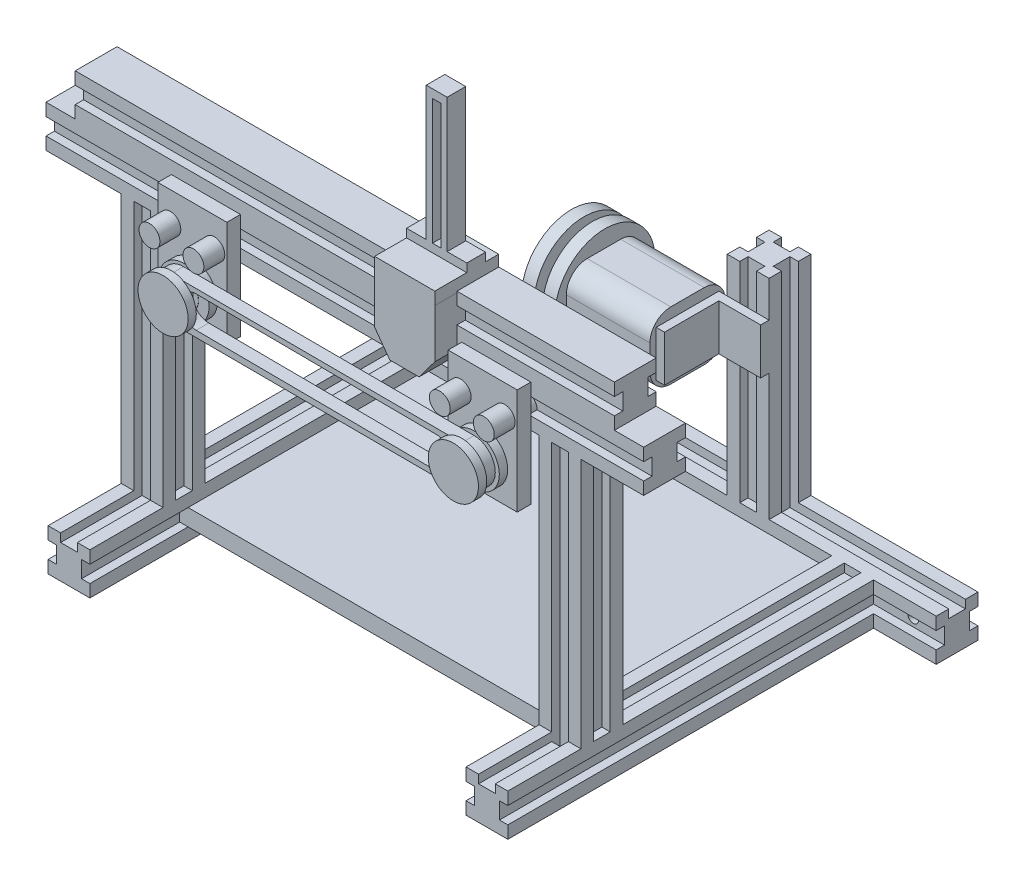
SolidWorks part; units mm, degrees
ref_plane "前基準面" through (0, 0, 0) normal (0, 0, 1) x (1, 0, 0)
ref_plane "上基準面" through (0, 0, 0) normal (0, 1, 0) x (1, 0, 0)
ref_plane "右基準面" through (0, 0, 0) normal (1, 0, 0) x (0, 0, -1)
sketch "草圖1" plane through (0, 0, 0) normal (0, 1, 0) x (1, 0, 0)
  line L1 (-5, 17.5) -> (5, 17.5)
  line L2 (-5, 17.5) -> (-5, -17.5)
  line L3 (-5, -17.5) -> (5, -17.5)
  line L4 (5, 17.5) -> (5, -17.5)
  line L5 (-5, 17.5) -> (5, -17.5) construction
  line L6 (-5, -17.5) -> (5, 17.5) construction
  point P0 (0, 0)
  dimension "D1" = 10
  dimension "D2" = 35
extrude "填料-伸長1" add sketch "草圖1" along normal blind 10
sketch "草圖2" plane through (0, 10, 0) normal (0, 1, 0) x (1, 0, 0)
  line L1 (-5, 17.5) -> (5, 17.5)
  line L2 (-5, 17.5) -> (-5, 27.5)
  line L3 (-5, 27.5) -> (5, 27.5)
  line L4 (5, 17.5) -> (5, 27.5)
  dimension "D1" = 10
extrude "填料-伸長2" add sketch "草圖2" along normal blind 60 and the other way blind 10
sketch "草圖3" plane through (0, 10, 0) normal (0, 1, 0) x (1, 0, 0)
  line L0 (0, -1017.5) -> (0, 48982.5) construction
  line L1 (-5, -17.5) -> (5, -17.5) construction
  line L2 (-5, 17.5) -> (5, 17.5) construction
  line L3 (-2, 17.5) -> (2, 17.5)
  line L4 (-2, 17.5) -> (-2, -17.5)
  line L5 (-2, -17.5) -> (2, -17.5)
  line L6 (2, 17.5) -> (2, -17.5)
  point P5 (0, -17.5)
  dimension "D1" = 2
  dimension "D2" = 2
extrude "除料-伸長1" cut sketch "草圖3" against normal blind 2
sketch "草圖5" plane through (0, 0, -17.5) normal (0, 0, 1) x (1, 0, 0)
  line L0 (0, -940) -> (0, 49060) construction
  line L1 (-5, 70) -> (5, 70) construction
  line L3 (-2, 8) -> (2, 8)
  line L4 (-2, 8) -> (-2, 70)
  line L5 (-2, 70) -> (2, 70)
  line L6 (2, 8) -> (2, 70)
  point P5 (0, 70)
  dimension "D1" = 0
extrude "除料-伸長2" cut sketch "草圖5" against normal blind 2
sketch "草圖6" plane through (0, 70, 0) normal (0, 1, 0) x (1, 0, 0)
  line L1 (-5, 27.5) -> (5, 27.5)
  line L2 (-5, 27.5) -> (-5, 17.5)
  line L3 (-5, 17.5) -> (5, 17.5)
  line L4 (5, 27.5) -> (5, 17.5)
extrude "填料-伸長3" add sketch "草圖6" along normal blind 10
sketch "草圖7" plane through (-5, 0, 0) normal (-1, 0, 0) x (0, 0, 1)
  line L0 (-17.5, 10) -> (-17.5, 80) construction
  line L1 (-27.5, 80) -> (-17.5, 80)
  line L2 (-27.5, 80) -> (-27.5, 70)
  line L3 (-27.5, 70) -> (-17.5, 70)
  line L4 (-17.5, 80) -> (-17.5, 70)
  dimension "D1" = 10
extrude "填料-伸長4" add sketch "草圖7" along normal blind 18
sketch "草圖9" plane through (5, 0, 0) normal (1, 0, 0) x (0, 0, -1)
  line L0 (27.5, 0) -> (27.5, 80) construction
  line L1 (17.5, 80) -> (27.5, 80)
  line L2 (17.5, 80) -> (17.5, 70)
  line L3 (17.5, 70) -> (27.5, 70)
  line L4 (27.5, 80) -> (27.5, 70)
  dimension "D1" = 10
extrude "填料-伸長6" add sketch "草圖9" along normal blind 100
sketch "草圖10" plane through (0, 0, -27.5) normal (0, 0, -1) x (-1, 0, 0)
  line L0 (0, -1000) -> (0, 49000) construction
  line L1 (-1005, 70) -> (48995, 70) construction
  line L2 (-5, 0) -> (5, 0) construction
  line L3 (-2, 70) -> (2, 70)
  line L4 (-2, 70) -> (-2, 0)
  line L5 (-2, 0) -> (2, 0)
  line L6 (2, 70) -> (2, 0)
  dimension "D1" = 0
  dimension "D2" = 2
  dimension "D3" = 2
extrude "除料-伸長3" cut sketch "草圖10" against normal blind 2
sketch "草圖12" plane through (0, 0, -27.5) normal (0, 0, -1) x (-1, 0, 0)
  line L0 (5, 0) -> (5, 70) construction
  line L1 (-5, 0) -> (5, 0)
  line L2 (-5, 0) -> (-5, 10)
  line L3 (-5, 10) -> (5, 10)
  line L4 (5, 0) -> (5, 10)
  dimension "D1" = 10
extrude "填料-伸長8" add sketch "草圖12" along normal blind 60
sketch "草圖13" plane through (0, 10, 0) normal (0, 1, 0) x (1, 0, 0)
  line L0 (2, -982.5) -> (2, 49017.5) construction
  line L1 (-2, -982.5) -> (-2, 49017.5) construction
  line L2 (-5, 87.5) -> (5, 87.5) construction
  line L3 (2, 27.5) -> (-2, 27.5)
  line L4 (2, 27.5) -> (2, 87.5)
  line L5 (2, 87.5) -> (-2, 87.5)
  line L6 (-2, 27.5) -> (-2, 87.5)
extrude "除料-伸長4" cut sketch "草圖13" against normal blind 2
sketch "草圖14" plane through (0, 0, -87.5) normal (0, 0, -1) x (-1, 0, 0)
  line L1 (-5, 10) -> (5, 10)
  line L2 (-5, 10) -> (-5, 0)
  line L3 (-5, 0) -> (5, 0)
  line L4 (5, 10) -> (5, 0)
extrude "填料-伸長9" add sketch "草圖14" along normal blind 10
sketch "草圖15" plane through (-5, 0, 0) normal (-1, 0, 0) x (0, 0, 1)
  line L0 (-97.5, 0) -> (17.5, 0) construction
  line L1 (-97.5, 10) -> (-87.5, 10)
  line L2 (-97.5, 10) -> (-97.5, 0)
  line L3 (-97.5, 0) -> (-87.5, 0)
  line L4 (-87.5, 10) -> (-87.5, 0)
  dimension "D1" = 10
extrude "填料-伸長10" add sketch "草圖15" along normal blind 15
sketch "草圖17" plane through (5, 0, 0) normal (1, 0, 0) x (0, 0, -1)
  line L0 (97.5, 10) -> (27.5, 10) construction
  line L1 (97.5, 0) -> (87.5, 0)
  line L2 (97.5, 0) -> (97.5, 10)
  line L3 (97.5, 10) -> (87.5, 10)
  line L4 (87.5, 0) -> (87.5, 10)
  dimension "D1" = 10
extrude "填料-伸長12" add sketch "草圖17" along normal blind 100
sketch "草圖18" plane through (0, 10, 0) normal (0, 1, 0) x (1, 0, 0)
  line L0 (105, 87.5) -> (80, 87.5) construction
  line L1 (105, 87.5) -> (5, 87.5) construction
  line L2 (-20, 97.5) -> (105, 97.5) construction
  line L3 (80, 87.5) -> (70, 87.5)
  line L4 (80, 87.5) -> (80, 97.5)
  line L5 (80, 97.5) -> (70, 97.5)
  line L6 (70, 87.5) -> (70, 97.5)
  dimension "D1" = 25
  dimension "D2" = 10
extrude "填料-伸長13" add sketch "草圖18" along normal blind 50
sketch "草圖19" plane through (0, 0, -87.5) normal (0, 0, 1) x (1, 0, 0)
  line L0 (75, -950) -> (75, 49050) construction
  line L1 (70, 60) -> (80, 60) construction
  line L3 (73, 60) -> (77, 60)
  line L4 (73, 60) -> (73, 10)
  line L5 (73, 10) -> (77, 10)
  line L6 (77, 60) -> (77, 10)
  point P5 (75, 60)
  dimension "D1" = 2
  dimension "D2" = 2
extrude "除料-伸長5" cut sketch "草圖19" against normal blind 2
sketch "草圖21" plane through (0, 0, -87.5) normal (0, 0, 1) x (1, 0, 0)
  line L0 (80, 60) -> (80, 10) construction
  line L1 (80, 51.343) -> (68, 51.343)
  line L2 (80, 51.343) -> (80, 40.343)
  line L3 (80, 40.343) -> (68, 40.343)
  line L4 (68, 51.343) -> (68, 40.343)
  dimension "D1" = 12
  dimension "D2" = 11
extrude "填料-伸長14" add sketch "草圖21" along normal blind 2
sketch "草圖22" plane through (0, 0, -87.5) normal (0, 0, -1) x (-1, 0, 0)
  line L1 (-70, 51.343) -> (-68, 51.343)
  line L2 (-70, 51.343) -> (-70, 40.343)
  line L3 (-70, 40.343) -> (-68, 40.343)
  line L4 (-68, 51.343) -> (-68, 40.343)
extrude "填料-伸長15" add sketch "草圖22" against normal blind 15
sketch "草圖26" plane through (0, 0, -87.5) normal (0, 0, 1) x (1, 0, 0)
  line L0 (105, 0) -> (5, 0) construction
  line L1 (105, 10) -> (95, 10)
  line L2 (105, 10) -> (105, 0)
  line L3 (105, 0) -> (95, 0)
  line L4 (95, 10) -> (95, 0)
  dimension "D1" = 10
extrude "填料-伸長18" add sketch "草圖26" along normal blind 60
sketch "草圖27" plane through (105, 0, 0) normal (1, 0, 0) x (0, 0, -1)
  line L1 (97.5, 0) -> (87.5, 0)
  line L2 (97.5, 0) -> (97.5, 10)
  line L3 (97.5, 10) -> (87.5, 10)
  line L4 (87.5, 0) -> (87.5, 10)
extrude "填料-伸長19" add sketch "草圖27" along normal blind 15
sketch "草圖29" plane through (0, 10, 0) normal (0, 1, 0) x (1, 0, 0)
  line L0 (-880, 92.5) -> (49120, 92.5) construction
  line L1 (120, 97.5) -> (120, 87.5) construction
  line L2 (-20, 87.5) -> (-20, 97.5) construction
  line L3 (-20, 94.5) -> (70, 94.5)
  line L4 (-20, 94.5) -> (-20, 90.5)
  line L5 (-20, 90.5) -> (70, 90.5)
  line L6 (70, 94.5) -> (70, 90.5)
  line L7 (70, 97.5) -> (70, 87.5) construction
  point P5 (120, 92.5)
  dimension "D1" = 2
  dimension "D2" = 2
extrude "除料-伸長6" cut sketch "草圖29" against normal blind 2
sketch "草圖30" plane through (80, 0, 0) normal (1, 0, 0) x (0, 0, -1)
  line L0 (92.5, -940) -> (92.5, 49060) construction
  line L1 (87.5, 60) -> (97.5, 60) construction
  line L2 (97.5, 10) -> (87.5, 10) construction
  line L3 (90.5, 60) -> (94.5, 60)
  line L4 (90.5, 60) -> (90.5, 10)
  line L5 (90.5, 10) -> (94.5, 10)
  line L6 (94.5, 60) -> (94.5, 10)
  point P5 (92.5, 60)
  dimension "D1" = 2
  dimension "D2" = 2
extrude "除料-伸長7" cut sketch "草圖30" against normal blind 2
sketch "草圖31" plane through (70, 0, 0) normal (-1, 0, 0) x (0, 0, 1)
  line L0 (-92.5, -940) -> (-92.5, 49060) construction
  line L1 (-97.5, 60) -> (-87.5, 60) construction
  line L3 (-94.5, 60) -> (-90.5, 60)
  line L4 (-94.5, 60) -> (-94.5, 8)
  line L5 (-94.5, 8) -> (-90.5, 8)
  line L6 (-90.5, 60) -> (-90.5, 8)
  point P5 (-92.5, 60)
extrude "除料-伸長8" cut sketch "草圖31" against normal blind 2
sketch "草圖32" plane through (0, 10, 0) normal (0, 1, 0) x (1, 0, 0)
  line L0 (120, 97.5) -> (120, 87.5) construction
  line L1 (78, 90.5) -> (120, 90.5)
  line L2 (78, 90.5) -> (78, 94.5)
  line L3 (78, 94.5) -> (120, 94.5)
  line L4 (120, 90.5) -> (120, 94.5)
  dimension "D1" = 0
extrude "除料-伸長9" cut sketch "草圖32" against normal blind 2
sketch "草圖33" plane through (0, 0, -17.5) normal (0, 0, 1) x (1, 0, 0)
  line L0 (-1023, 75) -> (48977, 75) construction
  line L1 (-23, 70) -> (-23, 80) construction
  line L2 (105, 80) -> (105, 70) construction
  line L3 (105, 77) -> (-23, 77)
  line L4 (105, 77) -> (105, 73)
  line L5 (105, 73) -> (-23, 73)
  line L6 (-23, 77) -> (-23, 73)
  point P5 (-23, 75)
  dimension "D1" = 2
  dimension "D2" = 2
  dimension "D3" = 0
extrude "除料-伸長10" cut sketch "草圖33" against normal blind 2
sketch "草圖34" plane through (0, 0, 0) normal (0, -1, 0) x (1, 0, 0)
  line L1 (95, -27.5) -> (105, -27.5)
  line L2 (95, -27.5) -> (95, -17.5)
  line L3 (95, -17.5) -> (105, -17.5)
  line L4 (105, -27.5) -> (105, -17.5)
extrude "填料-伸長21" add sketch "草圖34" against normal blind 72
sketch "草圖35" plane through (105, 0, 0) normal (1, 0, 0) x (0, 0, -1)
  line L1 (17.5, 80) -> (27.5, 80)
  line L2 (17.5, 80) -> (17.5, 70)
  line L3 (17.5, 70) -> (27.5, 70)
  line L4 (27.5, 80) -> (27.5, 70)
  dimension "D1" = 10
extrude "填料-伸長22" add sketch "草圖35" along normal blind 15
sketch "草圖37" plane through (0, 0, -17.5) normal (0, 0, 1) x (1, 0, 0)
  line L0 (120, 75) -> (115, 75) construction
  line L1 (120, 80) -> (120, 70) construction
  line L3 (105, 77) -> (115, 77)
  line L4 (105, 77) -> (105, 73)
  line L5 (105, 73) -> (115, 73)
  line L6 (115, 77) -> (115, 73)
  dimension "D1" = 5
extrude "除料-伸長11" cut sketch "草圖37" against normal blind 2
sketch "草圖38" plane through (0, 0, -17.5) normal (0, 0, 1) x (1, 0, 0)
  line L0 (-905, 70) -> (49095, 70) construction
  line L1 (100, -1000) -> (100, 49000) construction
  line L2 (105, 0) -> (95, 0) construction
  line L4 (98, 70) -> (102, 70)
  line L5 (98, 70) -> (98, 0)
  line L6 (98, 0) -> (102, 0)
  line L7 (102, 70) -> (102, 0)
  point P8 (100, 0)
  dimension "D1" = 2
  dimension "D2" = 2
extrude "除料-伸長12" cut sketch "草圖38" against normal blind 2
sketch "草圖40" plane through (0, 0, -17.5) normal (0, 0, 1) x (1, 0, 0)
  line L1 (95, 0) -> (105, 0)
  line L2 (95, 0) -> (95, 10)
  line L3 (95, 10) -> (105, 10)
  line L4 (105, 0) -> (105, 10)
extrude "填料-伸長23" add sketch "草圖40" along normal blind 35
sketch "草圖41" plane through (0, 10, 0) normal (0, 1, 0) x (1, 0, 0)
  line L0 (100, -1017.5) -> (100, 48982.5) construction
  line L1 (105, -17.5) -> (95, -17.5) construction
  line L2 (98, -1017.5) -> (98, 48982.5) construction
  line L3 (102, -1017.5) -> (102, 48982.5) construction
  line L5 (102, -17.5) -> (98, -17.5)
  line L6 (102, -17.5) -> (102, 17.5)
  line L7 (102, 17.5) -> (98, 17.5)
  line L8 (98, -17.5) -> (98, 17.5)
  line L9 (102, 27.3201) -> (98, 27.3201)
  line L10 (102, 27.3201) -> (102, 87.5)
  line L11 (102, 87.5) -> (98, 87.5)
  line L12 (98, 27.3201) -> (98, 87.5)
  point P5 (100, -17.5)
  dimension "D1" = 2
  dimension "D2" = 2
extrude "除料-伸長13" cut sketch "草圖41" against normal blind 2
sketch "草圖42" plane through (5, 0, 0) normal (1, 0, 0) x (0, 0, -1)
  line L0 (-912.5, 5) -> (49087.5, 5) construction
  line L1 (87.5, 10) -> (87.5, 0) construction
  line L2 (-912.5, 7) -> (49087.5, 7) construction
  line L3 (-912.5, 3) -> (49087.5, 3) construction
  line L4 (-17.5, 10) -> (-17.5, 0) construction
  line L5 (87.5, 7) -> (-17.5, 7)
  line L6 (87.5, 7) -> (87.5, 3)
  line L7 (87.5, 3) -> (-17.5, 3)
  line L8 (-17.5, 7) -> (-17.5, 3)
  point P5 (87.5, 5)
  dimension "D1" = 2
  dimension "D2" = 2
  dimension "D3" = 0
  dimension "D4" = 0
extrude "除料-伸長14" cut sketch "草圖42" against normal blind 2 and the other way blind 92
sketch "草圖43" plane through (0, 0, -27.5) normal (0, 0, -1) x (-1, 0, 0)
  line L0 (-100, -990) -> (-100, 49010) construction
  line L1 (-102, 10) -> (-98, 10) construction
  line L2 (-102, -929.9568) -> (-102, 49070.0432) construction
  line L3 (-98, -931.0163) -> (-98, 49068.9837) construction
  line L5 (-98, 10) -> (-102, 10)
  line L6 (-98, 10) -> (-98, 70)
  line L7 (-98, 70) -> (-102, 70)
  line L8 (-102, 10) -> (-102, 70)
  point P5 (-100, 10)
  dimension "D1" = 2
  dimension "D2" = 2
extrude "除料-伸長15" cut sketch "草圖43" against normal blind 2
sketch "草圖45" plane through (5, 0, 0) normal (1, 0, 0) x (0, 0, -1)
  line L0 (22.5, -930) -> (22.5, 49070) construction
  line L1 (17.5, 70) -> (27.5, 70) construction
  line L2 (20.5, -930) -> (20.5, 49070) construction
  line L3 (24.5, -930) -> (24.5, 49070) construction
  line L5 (20.5, 70) -> (24.5, 70)
  line L6 (20.5, 70) -> (20.5, 10)
  line L7 (20.5, 10) -> (24.5, 10)
  line L8 (24.5, 70) -> (24.5, 10)
  point P5 (22.5, 70)
  dimension "D1" = 2
  dimension "D2" = 2
extrude "除料-伸長17" cut sketch "草圖45" against normal blind 2 and the other way blind 92
sketch "草圖48" plane through (0, 0, -97.5) normal (0, 0, -1) x (-1, 0, 0)
  line L0 (-75, -940) -> (-75, 49060) construction
  line L1 (-80, 60) -> (-70, 60) construction
  line L2 (-1120, 5) -> (48880, 5) construction
  line L3 (-120, 0) -> (-120, 10) construction
  line L4 (-1120, 75) -> (48880, 75) construction
  line L5 (-120, 70) -> (-120, 80) construction
  line L6 (-1120, 77) -> (48880, 77) construction
  line L7 (-1120, 73) -> (48880, 73) construction
  line L8 (-1115.2458, 7) -> (48884.7542, 7) construction
  line L9 (-1115.2458, 3) -> (48884.7542, 3) construction
  line L10 (-77, -941.6109) -> (-77, 49058.3891) construction
  line L11 (-73, -943.2757) -> (-73, 49056.7243) construction
  line L12 (23, 80) -> (23, 70) construction
  line L13 (-120, 77) -> (23, 77)
  line L14 (-120, 77) -> (-120, 73)
  line L15 (-120, 73) -> (23, 73)
  line L16 (23, 77) -> (23, 73)
  line L17 (20, 10) -> (20, 0) construction
  line L18 (-120, 7) -> (20, 7)
  line L19 (-120, 7) -> (-120, 3)
  line L20 (-120, 3) -> (20, 3)
  line L21 (20, 7) -> (20, 3)
  line L23 (-77, 60) -> (-73, 60)
  line L24 (-77, 60) -> (-77, 10)
  line L25 (-77, 10) -> (-73, 10)
  line L26 (-73, 60) -> (-73, 10)
  point P5 (-75, 60)
  point P10 (-120, 5)
  point P15 (-120, 75)
  dimension "D1" = 2
  dimension "D2" = 2
  dimension "D3" = 2
  dimension "D4" = 2
  dimension "D5" = 2
  dimension "D6" = 2
  dimension "D7" = 0
extrude "除料-伸長19" cut sketch "草圖48" against normal blind 2
sketch "草圖49" plane through (0, 0, -27.5) normal (0, 0, -1) x (-1, 0, 0)
  line L0 (-1120, 75) -> (48880, 75) construction
  line L1 (-120, 70) -> (-120, 80) construction
  line L2 (-1115.2458, 77) -> (48884.7542, 77) construction
  line L3 (-1114.9431, 73) -> (48885.0569, 73) construction
  line L4 (23, 80) -> (23, 70) construction
  line L5 (-120.0173, 77) -> (23, 77)
  line L6 (-120.0173, 77) -> (-120.0173, 73)
  line L7 (-120.0173, 73) -> (23, 73)
  line L8 (23, 77) -> (23, 73)
  point P5 (-120, 75)
  dimension "D1" = 2
  dimension "D2" = 2
extrude "除料-伸長20" cut sketch "草圖49" against normal blind 2
sketch "草圖50" plane through (0, 0, -87.5) normal (0, 0, 1) x (1, 0, 0)
  line L1 (3, 7) -> (97, 7)
  line L2 (3, 7) -> (3, 3)
  line L3 (3, 3) -> (97, 3)
  line L4 (97, 7) -> (97, 3)
extrude "除料-伸長21" cut sketch "草圖50" against normal blind 2
sketch "草圖51" plane through (0, 0, -17.5) normal (0, 0, 1) x (1, 0, 0)
  line L0 (120, 80) -> (120, 70) construction
  line L1 (115, 77) -> (120, 77)
  line L2 (115, 77) -> (115, 73)
  line L3 (115, 73) -> (120, 73)
  line L4 (120, 77) -> (120, 73)
  dimension "D1" = 0
extrude "除料-伸長22" cut sketch "草圖51" against normal blind 2
sketch "草圖54" plane through (105, 0, 0) normal (1, 0, 0) x (0, 0, -1)
  line L0 (-1017.5, 5) -> (48982.5, 5) construction
  line L1 (-17.5, 0) -> (-17.5, 10) construction
  line L2 (-1012.3378, 7) -> (48987.6622, 7) construction
  line L3 (-1011.6075, 3) -> (48988.3925, 3) construction
  line L4 (87.5, 10) -> (87.5, 0) construction
  line L5 (-17.5, 7) -> (89.5, 7)
  line L6 (-17.5, 7) -> (-17.5, 3)
  line L7 (-17.5, 3) -> (89.5, 3)
  line L8 (89.5, 7) -> (89.5, 3)
  point P5 (-17.5, 5)
  dimension "D1" = 2
  dimension "D2" = 2
  dimension "D3" = 2
extrude "除料-伸長25" cut sketch "草圖54" along normal blind 24 and the other way blind 2
sketch "草圖55" plane through (-5, 0, 0) normal (-1, 0, 0) x (0, 0, 1)
  line L0 (-982.5, 5) -> (49017.5, 5) construction
  line L1 (17.5, 10) -> (17.5, 0) construction
  line L2 (-987.6622, 7) -> (49012.3378, 7) construction
  line L3 (-988.8794, 3) -> (49011.1206, 3) construction
  line L4 (-87.5, 0) -> (-87.5, 10) construction
  line L5 (17.5, 7) -> (-89.5, 7)
  line L6 (17.5, 7) -> (17.5, 3)
  line L7 (17.5, 3) -> (-89.5, 3)
  line L8 (-89.5, 7) -> (-89.5, 3)
  point P5 (17.5, 5)
  dimension "D1" = 2
  dimension "D2" = 2
  dimension "D3" = 2
extrude "除料-伸長26" cut sketch "草圖55" along normal blind 24 and the other way blind 2
sketch "草圖56" plane through (0, 0, -17.5) normal (0, 0, 1) x (1, 0, 0)
  line L0 (-12.5, -990) -> (-12.5, 49010) construction
  line L1 (-20, 10) -> (-5, 10) construction
  line L2 (112.5, -990) -> (112.5, 49010) construction
  line L3 (120, 10) -> (105, 10) construction
  line L4 (-20, 7) -> (-5, 7) construction
  line L5 (-3, 3) -> (-20, 3) construction
  line L6 (105, 7) -> (120, 7) construction
  line L7 (120, 3) -> (105, 3) construction
  circle A0 centre (-12.5, 5) radius 1.25
  circle A1 centre (112.5, 5) radius 1.25
  point P5 (-12.5, 10)
  point P10 (112.5, 10)
  dimension "D1" = 2.5
  dimension "D2" = 2
  dimension "D3" = 2
  dimension "D4" = 2
  dimension "D5" = 2
  dimension "D6" = 2.5
extrude "除料-伸長27" cut sketch "草圖56" against normal blind 81
sketch "草圖57" plane through (105, 0, 0) normal (1, 0, 0) x (0, 0, -1)
  line L0 (22.5, -930) -> (22.5, 49070) construction
  line L1 (17.5, 70) -> (27.5, 70) construction
  line L2 (20.5, -937.3112) -> (20.5, 49062.6888) construction
  line L3 (24.5, -938.6341) -> (24.5, 49061.3659) construction
  line L4 (17.5, 70) -> (27.5, 70) construction
  line L5 (24.5, 10.0144) -> (20.5, 10.0144)
  line L6 (24.5, 10.0144) -> (24.5, 70)
  line L7 (24.5, 70) -> (20.5, 70)
  line L8 (20.5, 10.0144) -> (20.5, 70)
  point P5 (22.5, 70)
  dimension "D1" = 2
  dimension "D2" = 2
extrude "除料-伸長28" cut sketch "草圖57" against normal blind 2
ref_plane "平面1" through (0, 0, -71) normal (0, 0, 1) x (1, 0, 0)
sketch "草圖64" plane through (0, 0, -89.5) normal (0, 0, 1) x (1, 0, 0)
  line L1 (3, 7) -> (97, 7)
  line L2 (3, 7) -> (3, 3)
  line L3 (3, 3) -> (97, 3)
  line L4 (97, 7) -> (97, 3)
extrude "填料-伸長29" add sketch "草圖64" along normal blind 66
sketch "草圖65" plane through (0, 80, 0) normal (0, 1, 0) x (1, 0, 0)
  line L0 (105, -17.5) -> (105, 17.5) construction
  line L1 (-5, -17.5) -> (105, -17.5)
  line L2 (-5, -17.5) -> (-5, 0)
  line L3 (-5, 0) -> (105, 0)
  line L4 (105, -17.5) -> (105, 0)
extrude "除料-伸長30" cut sketch "草圖65" against normal through all
ref_plane "平面2" through (0, 0, -11) normal (0, 0, 1) x (1, 0, 0)
sketch "草圖66" plane through (0, 0, -11) normal (0, 0, 1) x (1, 0, 0)
  line L0 (5, 70) -> (7, 70) construction
  line L1 (95, 70) -> (5, 70) construction
  line L2 (-23, 80) -> (120, 80) construction
  line L3 (7, 80) -> (23.5274, 80)
  line L4 (7, 80) -> (7, 54.6713)
  line L5 (7, 54.6713) -> (23.5274, 54.6713)
  line L6 (23.5274, 80) -> (23.5274, 54.6713)
  dimension "D1" = 2
extrude "填料-伸長30" add sketch "草圖66" against normal blind 6.5
sketch "草圖68" plane through (0, 80, 0) normal (0, 1, 0) x (1, 0, 0)
  line L0 (-44, 11) -> (44, 11) construction
  line L1 (7, 11) -> (23.5274, 11)
  line L2 (7, 11) -> (7, 14.25)
  line L3 (7, 14.25) -> (23.5274, 14.25)
  line L4 (23.5274, 11) -> (23.5274, 14.25)
  line L5 (7, 17.5) -> (7, 11) construction
  line L6 (23.5274, 17.5) -> (23.5274, 11) construction
extrude "除料-伸長32" cut sketch "草圖68" against normal through all
sketch "草圖69" plane through (0, 0, -14.25) normal (0, 0, 1) x (1, 0, 0)
  line L0 (-23, 73) -> (120, 73) construction
  line L1 (7, 73) -> (7, 70) construction
  line L2 (23.5274, 70) -> (23.5274, 73) construction
  circle A0 centre (10, 73) radius 2.5
  circle A1 centre (20.5274, 73) radius 2.5
  dimension "D2" = 5
  dimension "D3" = 5
  dimension "D1" = 3
  dimension "D4" = 3
extrude "填料-伸長31" add sketch "草圖69" along normal blind 5
sketch "草圖70" plane through (0, 0, -14.25) normal (0, 0, 1) x (1, 0, 0)
  line L0 (15.2637, -920) -> (15.2637, 49080) construction
  line L1 (23.5274, 80) -> (7, 80) construction
  circle A0 centre (15.2637, 62.3551) radius 6
  point P5 (15.2637, 80)
  dimension "D1" = 12
extrude "填料-伸長32" add sketch "草圖70" along normal blind 2
sketch "草圖71" plane through (0, 0, -12.25) normal (0, 0, 1) x (1, 0, 0)
  circle A0 centre (15.2637, 62.3551) radius 3.5
  dimension "D1" = 7
extrude "填料-伸長33" add sketch "草圖71" along normal blind 3
sketch "草圖72" plane through (0, 0, -9.25) normal (0, 0, 1) x (1, 0, 0)
  line L0 (15.2637, -934.1449) -> (15.2637, 49065.8551) construction
  line L1 (-984.7363, 62.3551) -> (49015.2637, 62.3551) construction
  circle A0 centre (15.2637, 62.3551) radius 6
extrude "填料-伸長34" add sketch "草圖72" along normal blind 2
sketch "草圖78" plane through (0, 80, 0) normal (0, 1, 0) x (1, 0, 0)
  line L0 (-993, 14.25) -> (49007, 14.25) construction
  line L1 (-992.5, 9.25) -> (49007.5, 9.25) construction
  line L2 (-990.6639, 7.25) -> (49009.3361, 7.25) construction
  line L4 (95, 17.5) -> (93, 17.5) construction
  line L5 (23.5274, 17.5) -> (120, 17.5) construction
  line L7 (93, 17.5) -> (76.47, 17.5)
  line L8 (93, 17.5) -> (93, 14.25)
  line L9 (93, 14.25) -> (76.47, 14.25)
  line L10 (76.47, 17.5) -> (76.47, 14.25)
  dimension "D1" = 2
  dimension "D2" = 16.53
extrude "填料-伸長38" add sketch "草圖78" against normal blind 29
sketch "草圖79" plane through (0, 0, -14.25) normal (0, 0, 1) x (1, 0, 0)
  line L0 (-977.1019, 73) -> (49022.8981, 73) construction
  line L1 (76.47, 70) -> (76.47, 73) construction
  line L2 (93, 70) -> (93, 73) construction
  circle A2 centre (79.47, 73) radius 2.5
  circle A3 centre (90, 73) radius 2.5
  dimension "D1" = 5
  dimension "D2" = 5
  dimension "D3" = 3
  dimension "D4" = 3
extrude "填料-伸長39" add sketch "草圖79" along normal blind 5 and the other way blind 9
sketch "草圖80" plane through (0, 0, -14.25) normal (0, 0, 1) x (1, 0, 0)
  line L0 (-993, 54.6713) -> (49007, 54.6713) construction
  line L1 (76.47, 51) -> (76.47, 80) construction
  line L2 (93, 51) -> (76.47, 51)
  line L3 (93, 51) -> (93, 54.6713)
  line L4 (93, 54.6713) -> (76.47, 54.6713)
  line L5 (76.47, 51) -> (76.47, 54.6713)
extrude "除料-伸長33" cut sketch "草圖80" against normal blind 5
sketch "草圖84" plane through (0, 0, -14.25) normal (0, 0, 1) x (1, 0, 0)
  line L0 (-990.7363, 62.3551) -> (49009.2637, 62.3551) construction
  line L1 (-992.5, 73) -> (49007.5, 73) construction
  circle A0 centre (84.7142, 62.3551) radius 6
  dimension "D1" = 12
extrude "填料-伸長43" add sketch "草圖84" along normal blind 2
sketch "草圖85" plane through (0, 0, -12.25) normal (0, 0, 1) x (1, 0, 0)
  circle A0 centre (84.6982, 62.3795) radius 3.5
  dimension "D1" = 7
extrude "填料-伸長44" add sketch "草圖85" along normal blind 3
sketch "草圖86" plane through (0, 0, -9.25) normal (0, 0, 1) x (1, 0, 0)
  circle A0 centre (84.7142, 62.3551) radius 6
extrude "填料-伸長45" add sketch "草圖86" along normal blind 2
ref_plane "平面3" through (0, 0, -12.2) normal (0, 0, 1) x (1, 0, 0)
sketch "草圖87" plane through (0, 0, -12.2) normal (0, 0, 1) x (1, 0, 0)
  line L0 (15.1647, 62.5846) -> (84.7142, 62.3551) construction
  line L1 (15.1815, 67.669) -> (84.731, 67.4394)
  line L2 (15.148, 57.5003) -> (84.6974, 57.2707)
  arc A0 (15.1815, 67.669) -> (15.148, 57.5003) centre (15.1647, 62.5846) ccw
  arc A1 (84.6974, 57.2707) -> (84.731, 67.4394) centre (84.7142, 62.3551) ccw
  point P3 (49.9395, 62.4698)
extrude "填料-伸長46" add sketch "草圖87" along normal blind 3
sketch "草圖89" plane through (0, 0, -9.2) normal (0, 0, 1) x (1, 0, 0)
  line L0 (21.2493, 62.77) -> (78.7142, 62.3749) construction
  line L1 (21.2753, 66.5377) -> (78.7402, 66.1425)
  line L2 (21.2234, 59.0024) -> (78.6883, 58.6072)
  arc A0 (18.773, 57.4883) -> (18.0679, 67.6595) centre (15.2637, 62.3551) ccw construction
  arc A1 (81.5452, 67.4499) -> (81.5117, 57.2812) centre (84.7142, 62.3551) ccw construction
  arc A2 (21.2753, 66.5377) -> (21.2234, 59.0024) centre (21.2493, 62.77) ccw
  arc A3 (78.6883, 58.6072) -> (78.7402, 66.1425) centre (78.7142, 62.3749) ccw
  point P8 (49.9818, 62.5724)
extrude "除料-伸長34" cut sketch "草圖89" against normal blind 3
sketch "草圖90" plane through (0, 80, 0) normal (0, 1, 0) x (1, 0, 0)
  line L0 (-1023, 22.5) -> (48977, 22.5) construction
  line L1 (-23, 17.5) -> (-23, 27.5) construction
  line L2 (93, 17.5) -> (120, 17.5) construction
  line L3 (-16.0037, 27.5) -> (113, 27.5)
  line L4 (-16.0037, 27.5) -> (-16.0037, 17.5)
  line L5 (-16.0037, 17.5) -> (113, 17.5)
  line L6 (113, 27.5) -> (113, 17.5)
  line L7 (-16.0037, 27.5) -> (113, 17.5) construction
  line L8 (-16.0037, 17.5) -> (113, 27.5) construction
  line L9 (120, 27.5) -> (120, 17.5) construction
  point P1 (48.4981, 22.5)
  point P5 (-23, 22.5)
  dimension "D1" = 6.9963
  dimension "D2" = 7
extrude "填料-伸長47" add sketch "草圖90" along normal blind 10
sketch "草圖91" plane through (0, 0, -17.5) normal (0, 0, 1) x (1, 0, 0)
  line L0 (-1016.0037, 85) -> (48983.9963, 85) construction
  line L1 (-16.0037, 90) -> (-16.0037, 80) construction
  line L2 (-1016.0037, 87) -> (48983.9963, 87) construction
  line L3 (-1016.0037, 83) -> (48983.9963, 83) construction
  line L4 (113, 90) -> (113, 80) construction
  line L5 (113, 83) -> (-16.7506, 83)
  line L6 (113, 83) -> (113, 87)
  line L7 (113, 87) -> (-16.7506, 87)
  line L8 (-16.7506, 83) -> (-16.7506, 87)
  point P5 (-16.0037, 85)
  dimension "D1" = 2
  dimension "D2" = 2
  dimension "D3" = 0
extrude "除料-伸長35" cut sketch "草圖91" against normal blind 2
sketch "草圖92" plane through (0, 0, -27.5) normal (0, 0, -1) x (-1, 0, 0)
  line L0 (-1113, 85) -> (48887, 85) construction
  line L1 (-113, 90) -> (-113, 80) construction
  line L2 (-1113, 87) -> (48887, 87) construction
  line L3 (-1113, 83) -> (48887, 83) construction
  line L5 (-114.6705, 87) -> (19.8373, 87)
  line L6 (-114.6705, 87) -> (-114.6705, 83)
  line L7 (-114.6705, 83) -> (19.8373, 83)
  line L8 (19.8373, 87) -> (19.8373, 83)
  point P5 (-113, 85)
extrude "除料-伸長36" cut sketch "草圖92" against normal blind 2
sketch "草圖94" plane through (0, 0, -12.2) normal (0, 0, 1) x (1, 0, 0)
  line L0 (60.925, 89.6673) -> (75.3197, 89.6673)
  line L1 (75.3197, 89.6673) -> (75.3197, 78)
  line L2 (75.3197, 78) -> (71.5615, 73)
  line L3 (23.5274, 73) -> (76.47, 73) construction
  line L4 (71.5615, 73) -> (64.5615, 73)
  line L5 (64.5615, 73) -> (60.925, 78)
  line L6 (60.925, 78) -> (60.925, 89.6673)
  dimension "D1" = 5
  dimension "D2" = 5
  dimension "D3" = 7
extrude "填料-伸長49" add sketch "草圖94" against normal blind 12
sketch "草圖95" plane through (0, 89.6673, 0) normal (0, 1, 0) x (1, 0, 0)
  line L0 (-69.667, 12.2) -> (69.667, 12.2) construction
  line L1 (60.925, 17.5) -> (75.328, 17.5)
  line L2 (60.925, 17.5) -> (60.925, 12.2)
  line L3 (60.925, 12.2) -> (75.328, 12.2)
  line L4 (75.328, 17.5) -> (75.328, 12.2)
extrude "填料-伸長50" add sketch "草圖95" along normal blind 3
sketch "草圖96" plane through (0, 0, -17.5) normal (0, 0, -1) x (-1, 0, 0)
  line L0 (-113, 90) -> (16.0037, 90) construction
  line L1 (-75.328, 92.6673) -> (-60.925, 92.6673)
  line L2 (-75.328, 92.6673) -> (-75.328, 90)
  line L3 (-75.328, 90) -> (-60.925, 90)
  line L4 (-60.925, 92.6673) -> (-60.925, 90)
  line L5 (-60.925, 92.6673) -> (-60.925, 90) construction
extrude "填料-伸長51" add sketch "草圖96" along normal blind 10
sketch "草圖97" plane through (0, 92.6673, 0) normal (0, 1, 0) x (1, 0, 0)
  line L0 (-939.075, 22.5) -> (49060.925, 22.5) construction
  line L1 (60.925, 27.5) -> (60.925, 17.5) construction
  line L2 (75.328, 12.2) -> (75.328, 27.5) construction
  line L3 (60.925, 24.3312) -> (75.328, 24.3312)
  line L4 (60.925, 24.3312) -> (60.925, 19.85)
  line L5 (60.925, 19.85) -> (75.328, 19.85)
  line L6 (75.328, 24.3312) -> (75.328, 19.85)
  point P5 (60.925, 22.5)
extrude "填料-伸長52" add sketch "草圖97" along normal blind 2
sketch "草圖98" plane through (0, 94.6673, 0) normal (0, 1, 0) x (1, 0, 0)
  line L0 (68.1265, -975.6688) -> (68.1265, 49024.3312) construction
  line L1 (75.328, 24.3312) -> (60.925, 24.3312) construction
  line L2 (60.925, 19.85) -> (75.328, 19.85) construction
  line L3 (65.6265, 24.2969) -> (70.6265, 24.2969)
  line L4 (65.6265, 24.2969) -> (65.6265, 19.85)
  line L5 (65.6265, 19.85) -> (70.6265, 19.85)
  line L6 (70.6265, 24.2969) -> (70.6265, 19.85)
  line L7 (65.6265, 24.2969) -> (70.6265, 19.85) construction
  line L8 (65.6265, 19.85) -> (70.6265, 24.2969) construction
  point P1 (68.1265, 22.0734)
  point P5 (68.1265, 24.3312)
  dimension "D1" = 5
extrude "填料-伸長53" add sketch "草圖98" along normal blind 32
sketch "草圖99" plane through (68, 0, 0) normal (-1, 0, 0) x (0, 0, 1)
  line L0 (-80, -948.657) -> (-80, 49051.343) construction
  line L1 (-72.5, 51.343) -> (-87.5, 51.343) construction
  line L2 (-1087.5, 45.843) -> (48912.5, 45.843) construction
  line L3 (-87.5, 51.343) -> (-87.5, 40.343) construction
  line L5 (-89, 53.843) -> (-71, 53.843)
  line L6 (-89, 53.843) -> (-89, 37.843)
  line L7 (-89, 37.843) -> (-71, 37.843)
  line L8 (-71, 53.843) -> (-71, 37.843)
  line L9 (-89, 53.843) -> (-71, 37.843) construction
  line L10 (-89, 37.843) -> (-71, 53.843) construction
  point P5 (-80, 51.343)
  point P6 (-80, 45.843)
  point P10 (-87.5, 45.843)
  dimension "D1" = 18
  dimension "D2" = 16
extrude "填料-伸長54" add sketch "草圖99" along normal blind 20
fillet "圓角1" radius 5 4 edges at (58, 37.843, -89) (58, 37.843, -71) (58, 53.843, -89) (58, 53.843, -71)
sketch "草圖100" plane through (48, 0, 0) normal (-1, 0, 0) x (0, 0, 1)
  circle A0 centre (-80.2283, 45.9747) radius 11.9386
extrude "填料-伸長55" add sketch "草圖100" along normal blind 3
sketch "草圖101" plane through (45, 0, 0) normal (-1, 0, 0) x (0, 0, 1)
  line L0 (-1092.1669, 45.9747) -> (48907.8331, 45.9747) construction
  line L1 (-80.2283, -942.0867) -> (-80.2283, 49057.9133) construction
  circle A2 centre (-80.2283, 45.9747) radius 7.6024
extrude "填料-伸長56" add sketch "草圖101" along normal blind 2
sketch "草圖102" plane through (43, 0, 0) normal (-1, 0, 0) x (0, 0, 1)
  line L0 (-80.2283, -946.4229) -> (-80.2283, 49053.5771) construction
  line L1 (-1087.8307, 45.9747) -> (48912.1693, 45.9747) construction
  circle A4 centre (-80.2283, 45.9747) radius 11.9386
extrude "填料-伸長57" add sketch "草圖102" along normal blind 3
sketch "草圖103" plane through (40, 0, 0) normal (-1, 0, 0) x (0, 0, 1)
  line L0 (-80.2283, -942.0867) -> (-80.2283, 49057.9133) construction
  line L1 (-1092.1669, 45.9747) -> (48907.8331, 45.9747) construction
  circle A1 centre (-80.2283, 45.9747) radius 7.3698
extrude "填料-伸長58" add sketch "草圖103" along normal blind 3
sketch "草圖104" plane through (0, 0, -12.2) normal (0, 0, 1) x (1, 0, 0)
  line L0 (40, 57.9133) -> (40, 34.0361) construction
  line L1 (40, 49.1707) -> (34.0983, 49.1707)
  line L2 (40, 49.1707) -> (40, 46.3781)
  line L3 (40, 46.3781) -> (34.0983, 46.3781)
  line L4 (34.0983, 49.1707) -> (34.0983, 46.3781)
extrude "除料-伸長37" cut sketch "草圖104" against normal blind 69
sketch "草圖106" plane through (0, 0, -19.85) normal (0, 0, 1) x (1, 0, 0)
  line L0 (65.6265, 126.6673) -> (65.6265, 94.6673) construction
  line L1 (67.1265, 124.6673) -> (69.1265, 124.6673)
  line L2 (67.1265, 124.6673) -> (67.1265, 94.6673)
  line L3 (67.1265, 94.6673) -> (69.1265, 94.6673)
  line L4 (69.1265, 124.6673) -> (69.1265, 94.6673)
  line L5 (70.6265, 126.6673) -> (70.6265, 94.6673) construction
  line L6 (65.6265, 126.6673) -> (70.6265, 126.6673) construction
  dimension "D1" = 1.5
  dimension "D2" = 1.5
  dimension "D3" = 2
extrude "除料-伸長38" cut sketch "草圖106" against normal blind 10
